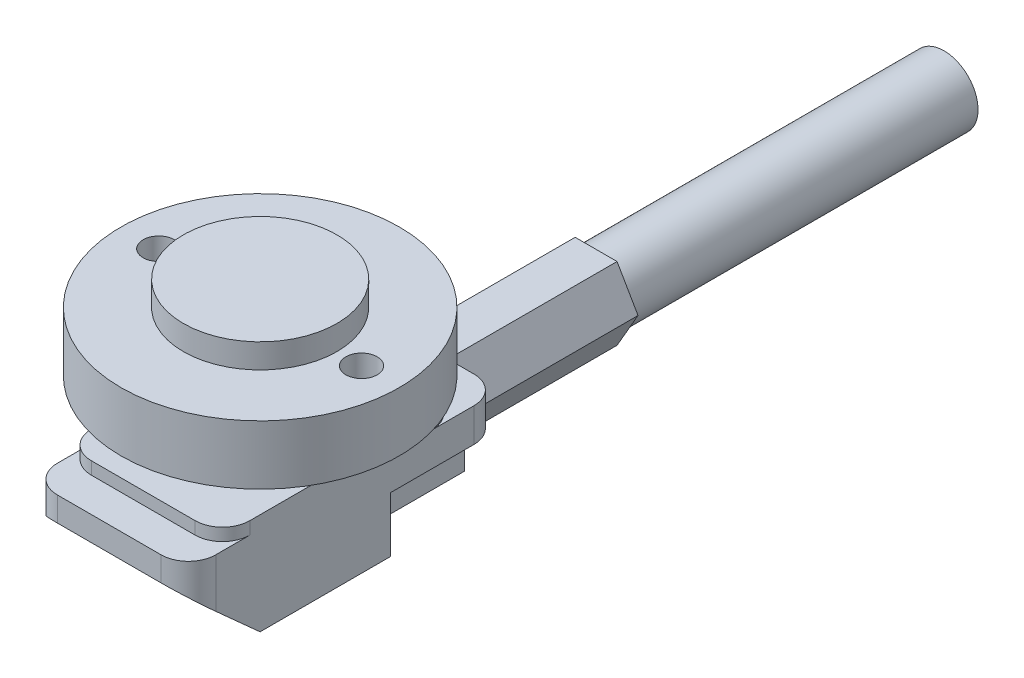
SolidWorks part; units mm, degrees
ref_plane "Front Plane" through (0, 0, 0) normal (0, 0, 1) x (1, 0, 0)
ref_plane "Top Plane" through (0, 0, 0) normal (0, 1, 0) x (1, 0, 0)
ref_plane "Right Plane" through (0, 0, 0) normal (1, 0, 0) x (0, 0, -1)
sketch "Sketch1" plane through (0, 0, 0) normal (0, 1, 0) x (1, 0, 0)
  circle A0 centre (0, 0) radius 5.6071
  dimension "D1" = 11.2141
extrude "Boss-Extrude1" add sketch "Sketch1" against normal blind 1.778
sketch "Sketch2" plane through (0, -1.778, 0) normal (0, -1, 0) x (1, 0, 0)
  circle A0 centre (0, 0) radius 10.16
  dimension "D1" = 20.32
extrude "Boss-Extrude2" add sketch "Sketch2" along normal blind 4.318
sketch "Sketch3" plane through (0, -1.778, 0) normal (0, 1, 0) x (1, 0, 0)
  circle A0 centre (7.4, 0) radius 1.143
  point P5 (0, 0)
  dimension "D2" = 2.286
  dimension "D1" = 7.4
extrude "Cut-Extrude1" cut sketch "Sketch3" against normal blind 3.318
mirror "Mirror1" about plane through (0, 0, 0) normal (1, 0, 0) of "Cut-Extrude1"
sketch "Sketch4" plane through (0, -6.096, 0) normal (0, -1, 0) x (1, 0, 0)
  circle A0 centre (0, 0) radius 5.5626
  dimension "D1" = 11.1252
extrude "Boss-Extrude3" add sketch "Sketch4" along normal blind 3.0099
sketch "Sketch5" plane through (0, 0, 0) normal (1, 0, 0) x (0, 0, -1)
  line L0 (-8.5344, -9.1059) -> (8.7757, -9.1059)
  line L1 (8.7757, -9.1059) -> (8.7757, -10.0203)
  line L2 (8.7757, -10.0203) -> (11.8237, -10.0203)
  line L3 (11.8237, -10.0203) -> (11.8237, -16.51)
  line L4 (11.8237, -16.51) -> (-5.7912, -16.51)
  line L5 (-5.7912, -16.51) -> (-11.0236, -11.7983)
  line L6 (-11.0236, -11.7983) -> (-11.0236, -10.0203)
  line L7 (-11.0236, -10.0203) -> (-8.5344, -10.0203)
  line L8 (-8.5344, -10.0203) -> (-8.5344, -9.1059)
  line L9 (-5.5626, -9.1059) -> (5.5626, -9.1059) construction
  dimension "D1" = 6.4897
  dimension "D2" = 7.4041
  dimension "D3" = 17.6149
  dimension "D4" = 3.048
  dimension "D5" = 11.8237
  dimension "D6" = 2.4892
  dimension "D7" = 1.778
  dimension "D8" = 11.0236
extrude "Boss-Extrude4" add sketch "Sketch5" along normal mid plane 11.5697
fillet "Fillet1" radius 2 4 edges at (-5.7849, -9.5631, -8.7757) (5.7849, -9.5631, -8.7757) (-5.7849, -9.5631, 8.5344) (5.7849, -9.5631, 8.5344)
fillet "Fillet2" radius 2 2 edges at (-5.7849, -10.9093, 11.0236) (5.7849, -10.9093, 11.0236)
sketch "Sketch6" plane through (5.7849, 0, 0) normal (1, 0, 0) x (0, 0, -1)
  line L1 (11.8237, -16.51) -> (3.7465, -16.51)
  line L2 (11.8237, -16.51) -> (11.8237, -12.4714)
  line L3 (11.8237, -12.4714) -> (3.7465, -12.4714)
  line L4 (3.7465, -16.51) -> (3.7465, -12.4714)
  dimension "D1" = 8.0772
  dimension "D2" = 4.0386
extrude "Cut-Extrude2" cut sketch "Sketch6" against normal blind 2.6924
chamfer "Chamfer1" distance 2.6924 angle 45 1 edges at (3.0925, -14.4907, -3.7465)
mirror "Mirror2" about plane through (0, 0, 0) normal (1, 0, 0) of "Cut-Extrude2", "Chamfer1"
fillet "Fillet3" radius 2 2 edges at (-5.7849, -11.2459, -11.8237) (5.7849, -11.2459, -11.8237)
sketch "Sketch7" plane through (0, 0, -11.8237) normal (0, 0, -1) x (-1, 0, 0)
  line L1 (1.53, -15.6811) -> (3.06, -13.0311)
  line L2 (3.06, -13.0311) -> (1.53, -10.3811)
  line L3 (1.53, -10.3811) -> (-1.53, -10.3811)
  line L4 (-1.53, -10.3811) -> (-3.06, -13.0311)
  line L5 (-3.06, -13.0311) -> (-1.53, -15.6811)
  line L6 (-1.53, -15.6811) -> (1.53, -15.6811)
  circle A0 centre (0, -13.0311) radius 2.65 construction
  dimension "D1" = 5.3
  dimension "D2" = 13.0311
extrude "Boss-Extrude5" add sketch "Sketch7" along normal blind 12.7
sketch "Sketch8" plane through (0, 0, -24.5237) normal (0, 0, -1) x (-1, 0, 0)
  line L0 (-1.53, -10.3811) -> (-3.06, -13.0311) construction
  circle A0 centre (0, -13.0077) radius 2.6383 construction
  circle A1 centre (0, -13.0077) radius 2.4828
  dimension "D1" = 4.9657
extrude "Boss-Extrude6" add sketch "Sketch8" along normal blind 25.4
